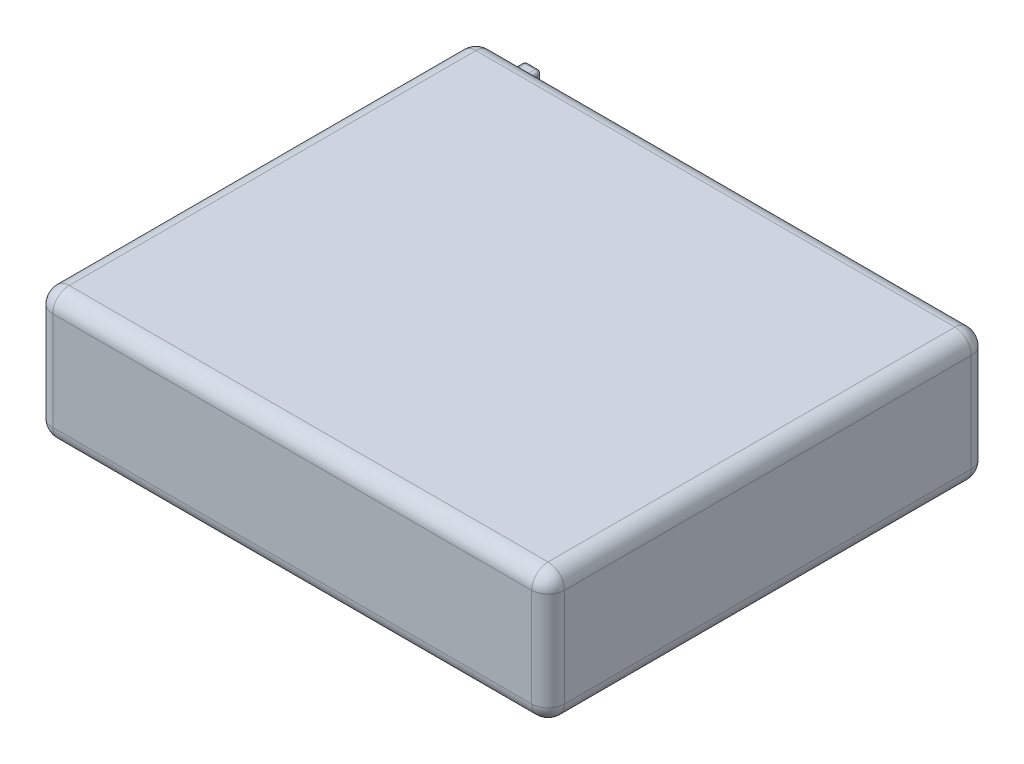
SolidWorks part; units mm, degrees
ref_plane "Front Plane" through (0, 0, 0) normal (0, 0, 1) x (1, 0, 0)
ref_plane "Top Plane" through (0, 0, 0) normal (0, 1, 0) x (1, 0, 0)
ref_plane "Right Plane" through (0, 0, 0) normal (1, 0, 0) x (0, 0, -1)
sketch "Sketch1" plane through (0, 0, 0) normal (0, 1, 0) x (1, 0, 0)
  line L0 (-87.7694, 0) -> (104.6609, 0) construction
  line L1 (-39, 33.5) -> (39, 33.5)
  line L2 (-39, 33.5) -> (-39, -33.5)
  line L3 (-39, -33.5) -> (39, -33.5)
  line L4 (39, 33.5) -> (39, -33.5)
  line L5 (0, 62.117) -> (0, -51.4598) construction
  point P0 (0, 0)
  dimension "D1" = 78
  dimension "D2" = 67
extrude "Boss-Extrude1" add sketch "Sketch1" along normal blind 10 and the other way blind 10
fillet "Fillet1" radius 2.5 12 edges at (-39, -10, 0) (0, -10, -33.5) (-39, 0, -33.5) (39, -10, 0) (39, 0, -33.5) (0, -10, 33.5) (-39, 0, 33.5) (39, 0, 33.5) (0, 10, 33.5) (-39, 10, 0) (0, 10, -33.5) (39, 10, 0)
sketch "Sketch2" plane through (0, 0, -33.5) normal (0, 0, -1) x (-1, 0, 0)
  line L1 (36.5, -7.5) -> (36.5, 7.5) construction
  line L2 (34, 5) -> (36.5, 5)
  line L3 (34, 5) -> (34, -5)
  line L4 (34, -5) -> (36.5, -5)
  line L5 (36.5, 5) -> (36.5, -5)
  line L6 (36.5, 7.5) -> (-36.5, 7.5) construction
  line L7 (-36.5, -7.5) -> (36.5, -7.5) construction
  dimension "D1" = 2.5
  dimension "D2" = 2.5
  dimension "D3" = 2.5
extrude "Boss-Extrude2" add sketch "Sketch2" along normal blind 5
fillet "Fillet2" radius 0.5 12 edges at (-34, 0, -33.5) (-34, -5, -36) (-35.25, -5, -33.5) (-35.25, -5, -38.5) (-34, 0, -38.5) (-35.25, 5, -38.5) (-34, 5, -36) (-35.25, 5, -33.5) (-36.5, -5, -36) (-36.5, 0, -38.5) (-36.5, 5, -36) (-36.5, 0, -33.5)
